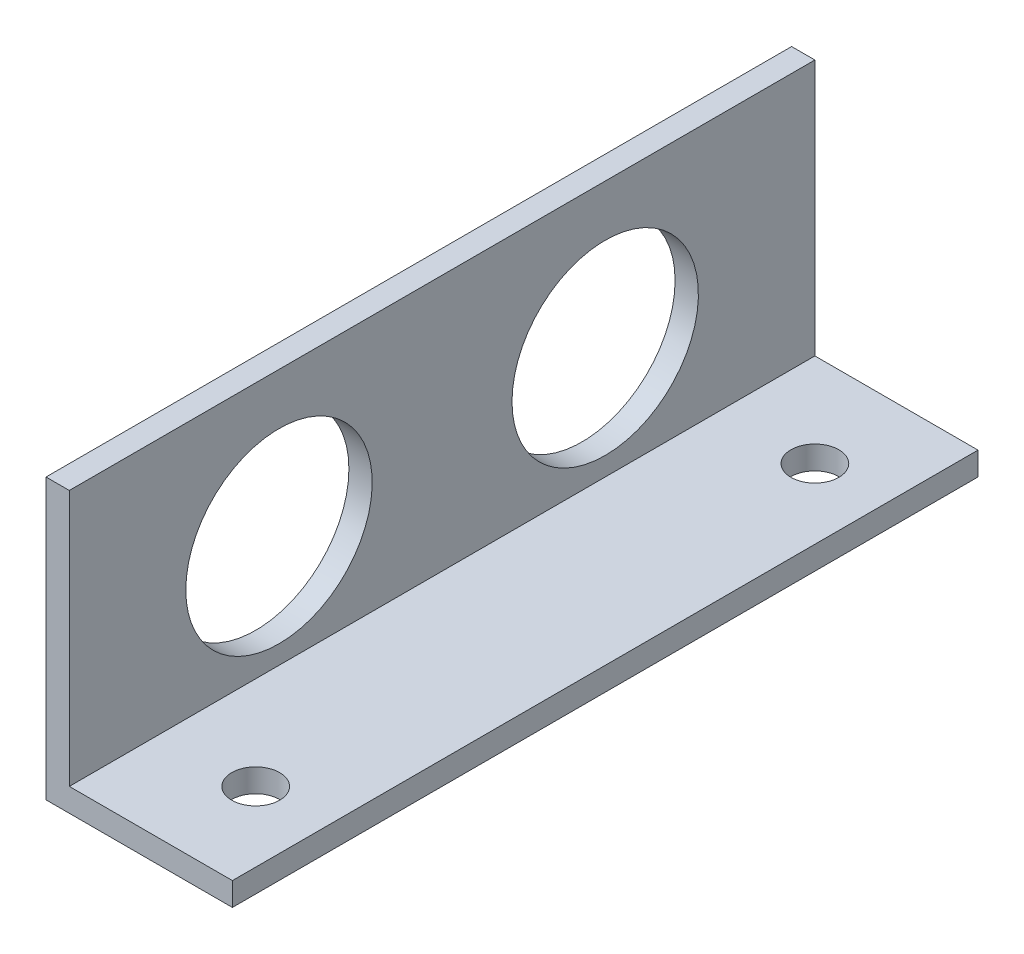
SolidWorks part; units mm, degrees
ref_plane "Front Plane" through (0, 0, 0) normal (0, 0, 1) x (1, 0, 0)
ref_plane "Top Plane" through (0, 0, 0) normal (0, 1, 0) x (1, 0, 0)
ref_plane "Right Plane" through (0, 0, 0) normal (1, 0, 0) x (0, 0, -1)
sketch "Sketch1" plane through (0, 0, 0) normal (0, 0, 1) x (1, 0, 0)
  line L0 (0, 0) -> (12.7, 0)
  line L1 (55, 0) -> (-55, 0) construction
  line L2 (12.7, 0) -> (12.7, 1.5875)
  line L3 (12.7, 1.5875) -> (1.5875, 1.5875)
  line L4 (1.5875, 1.5875) -> (1.5875, 19.05)
  line L5 (1.5875, 19.05) -> (0, 19.05)
  line L6 (0, -55) -> (0, 55) construction
  line L7 (0, 19.05) -> (0, 0)
  dimension "D1" = 1.5875
  dimension "D2" = 12.7
  dimension "D3" = 19.05
extrude "Boss-Extrude1" add sketch "Sketch1" along normal mid plane 50.8
sketch "Sketch3" plane through (0, 0, 0) normal (-1, 0, 0) x (0, 0, 1)
  line L0 (0, 0) -> (0, 9.2075) construction
  line L1 (0, 9.2075) -> (11.1125, 9.2075) construction
  line L2 (0, 9.2075) -> (-11.1125, 9.2075) construction
  line L3 (25.4, 0) -> (-25.4, 0) construction
  circle A0 centre (11.1125, 9.2075) radius 6.35
  circle A1 centre (-11.1125, 9.2075) radius 6.35
  dimension "D1" = 12.7
  dimension "D2" = 22.225
  dimension "D3" = 9.2075
extrude "Cut-Extrude1" cut sketch "Sketch3" against normal through all
sketch "Sketch5" plane through (0, 1.5875, 0) normal (0, 1, 0) x (1, 0, 0)
  line L0 (1.5875, 0) -> (7.9375, 0) construction
  line L1 (1.5875, -25.4) -> (1.5875, 25.4) construction
  line L2 (7.9375, 0) -> (7.9375, 19.05) construction
  line L3 (7.9375, 0) -> (7.9375, -19.05) construction
  line L4 (12.7, 25.4) -> (1.5875, 25.4) construction
  dimension "D1" = 6.35
  dimension "D2" = 6.35
  dimension "D3" = 38.1
hole_wizard "#4 Clearance Hole1" positions "Sketch10" profile "Sketch9" hole size "#4" standard "ANSI Inch"
sketch "Sketch10" plane through (0, 1.5875, 0) normal (0, 1, 0) x (1, 0, 0)
  point P0 (7.9375, 19.05)
  point P3 (7.9375, -19.05)
sketch "Sketch9" plane through (7.9375, 1.5875, -19.05) normal (1, 0, 0) x (0, 0, 1)
  line L0 (0, 0) -> (0, 4.1556)
  line L1 (0, 4.1556) -> (1.6319, 3.175)
  line L2 (1.6319, 3.175) -> (1.6319, 0)
  line L5 (1.6319, 0) -> (0, 0)
  line L10 (0, 4.1556) -> (-1.632, 3.175) construction
  line L11 (0, -6.35) -> (0, 107.95) construction
  dimension "Hole Dia." = 3.2639
  dimension "Hole Depth" = 3.175
  dimension "Drill Angle" = 118
